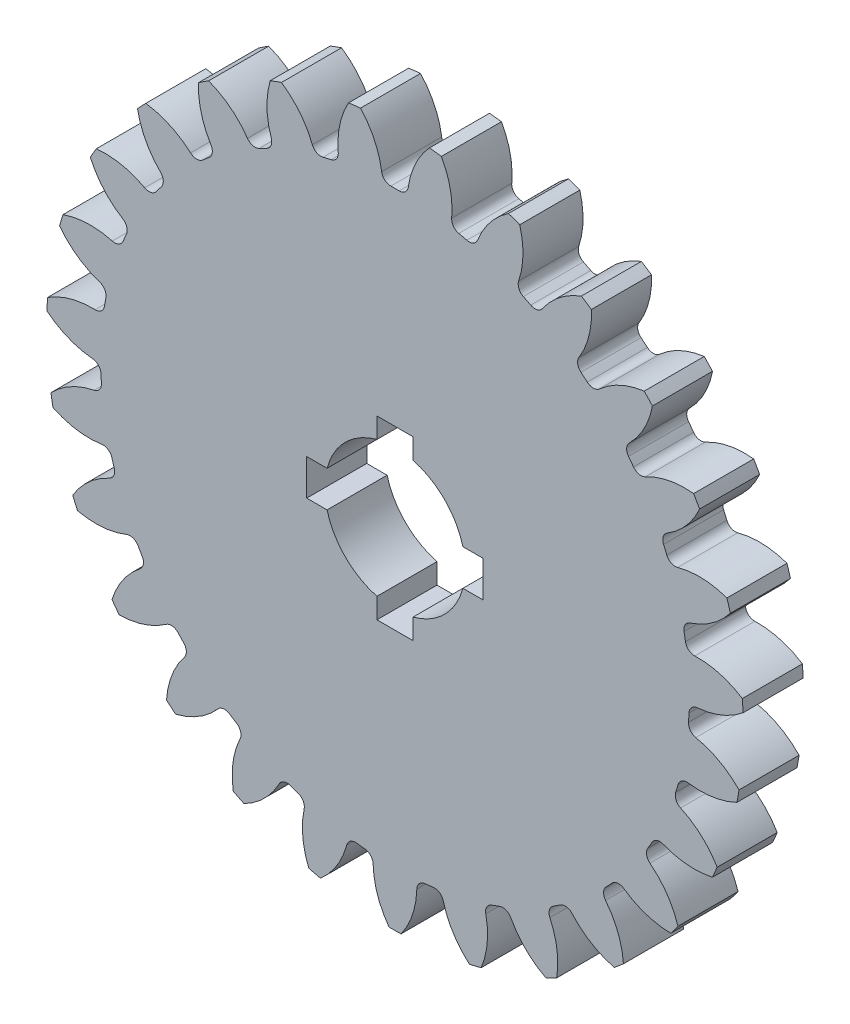
SolidWorks part; units mm, degrees
ref_plane "Front Plane" through (0, 0, 0) normal (0, 0, 1) x (1, 0, 0)
ref_plane "Top Plane" through (0, 0, 0) normal (0, 1, 0) x (1, 0, 0)
ref_plane "Right Plane" through (0, 0, 0) normal (1, 0, 0) x (0, 0, -1)
sketch "Sketch1" plane through (0, 0, 0) normal (0, 0, 1) x (1, 0, 0)
  line L4 (-1.0463, 24.4776) -> (0, 0) construction
  line L5 (0, 0) -> (0, 29) construction
  line L6 (0, 0) -> (3.3667, 28.8039) construction
  line L7 (-1.6208, 26.9513) -> (0.7728, 27.9892) construction
  line L8 (-1.6208, 26.9513) -> (0.4007, 27.0729) construction
  line L11 (1.6208, 26.9513) -> (-1.6208, 26.9513) construction
  circle A0 centre (0, 0) radius 24.5
  circle A1 centre (0, 0) radius 27 construction
  circle A2 centre (0, 0) radius 29
  arc A3 (-2.8696, 28.8577) -> (-1.0463, 24.4776) centre (-7.9254, 24.1836) cw
  arc A4 (2.8696, 28.8577) -> (1.0463, 24.4776) centre (7.9254, 24.1836) ccw
  point P5 (-27, 0)
  point P6 (-29, 0)
  point P7 (-24.5, 0)
  point P12 (-1.6208, 26.9513)
  point P22 (1.6208, 26.9513)
  dimension "D5" = 54
  dimension "D1" = 2.5
  dimension "D2" = 2
  dimension "D3" = 20
  dimension "D4" = 3.2416
  dimension "D6" = 6.667
  dimension "D7" = 0.5
extrude "Boss-Extrude1" add sketch "Sketch1" against normal blind 5 contours A2
extrude "Cut-Extrude1" cut sketch "Sketch1<4>" against normal blind 10 contours A4 A2 A3 A0 region at (0, 27.1314, 0)
sketch "Sketch1<4>" plane through (0, 0, 0) normal (0, 0, 1) x (1, 0, 0) same geometry as "Sketch1"
fillet "Fillet2" radius 0.76 2 edges at (1.0463, 24.4776, -2.5) (-1.0463, 24.4776, -2.5)
ref_axis "Axis1" through (0, 0, 0) along (0, 0, 1)
pattern_circular "CirPattern2" count 27 over 360 about axis through (0, 0, 0) along (0, 0, 1) of "Cut-Extrude1", "Fillet2"
sketch "Sketch2" plane through (0, 0, 0) normal (0, 0, 1) x (1, 0, 0)
  line L0 (-1.5, 5.6528) -> (-1.5, 7.3485)
  line L1 (-1.5, 4.3485) -> (1.5, 4.3485) construction
  line L2 (-1.5, 4.3485) -> (-1.5, 7.3485) construction
  line L3 (-1.5, 7.3485) -> (1.5, 7.3485) construction
  line L4 (1.5, 4.3485) -> (1.5, 7.3485) construction
  line L5 (-1.5, 4.3485) -> (1.5, 7.3485) construction
  line L6 (-1.5, 7.3485) -> (1.5, 4.3485) construction
  line L7 (4.3485, -1.5) -> (7.3485, -1.5) construction
  line L8 (4.3485, -1.5) -> (4.3485, 1.5) construction
  line L9 (4.3485, 1.5) -> (7.3485, 1.5) construction
  line L10 (7.3485, -1.5) -> (7.3485, 1.5) construction
  line L11 (4.3485, -1.5) -> (7.3485, 1.5) construction
  line L12 (4.3485, 1.5) -> (7.3485, -1.5) construction
  line L13 (-1.5, -7.3485) -> (1.5, -7.3485) construction
  line L14 (-1.5, -7.3485) -> (-1.5, -4.3485) construction
  line L15 (-1.5, -4.3485) -> (1.5, -4.3485) construction
  line L16 (1.5, -7.3485) -> (1.5, -4.3485) construction
  line L17 (-1.5, -7.3485) -> (1.5, -4.3485) construction
  line L18 (-1.5, -4.3485) -> (1.5, -7.3485) construction
  line L19 (-7.3485, -1.5) -> (-4.3485, -1.5) construction
  line L20 (-7.3485, -1.5) -> (-7.3485, 1.5) construction
  line L21 (-7.3485, 1.5) -> (-4.3485, 1.5) construction
  line L22 (-4.3485, -1.5) -> (-4.3485, 1.5) construction
  line L23 (-7.3485, -1.5) -> (-4.3485, 1.5) construction
  line L24 (-7.3485, 1.5) -> (-4.3485, -1.5) construction
  line L25 (-1.5, 7.3485) -> (1.5, 7.3485)
  line L26 (1.5, 7.3485) -> (1.5, 5.6528)
  line L27 (5.6528, 1.5) -> (7.3485, 1.5)
  line L28 (7.3485, 1.5) -> (7.3485, -1.5)
  line L29 (7.3485, -1.5) -> (5.6528, -1.5)
  line L30 (1.5, -7.3485) -> (1.5, -5.6528)
  line L31 (1.5, -7.3485) -> (-1.5, -7.3485)
  line L32 (-1.5, -7.3485) -> (-1.5, -5.6528)
  line L33 (-5.6528, -1.5) -> (-7.3485, -1.5)
  line L34 (-7.3485, -1.5) -> (-7.3485, 1.5)
  line L35 (-7.3485, 1.5) -> (-5.6528, 1.5)
  circle A0 centre (0, 0) radius 7.5 construction
  arc A1 (-1.5, 5.6528) -> (-5.6528, 1.5) centre (0, 0) ccw
  arc A2 (5.6528, 1.5) -> (1.5, 5.6528) centre (0, 0) ccw
  arc A3 (1.5, -5.6528) -> (5.6528, -1.5) centre (0, 0) ccw
  arc A4 (-5.6528, -1.5) -> (-1.5, -5.6528) centre (0, 0) ccw
  point P3 (0, 5.8485)
  point P8 (5.8485, 0)
  point P13 (0, -5.8485)
  point P18 (-5.8485, 0)
  dimension "D1" = 15
  dimension "D2" = 3
extrude "Cut-Extrude2" cut sketch "Sketch2" against normal up to surface (5 mm away) up to face at (0, 0, -5)
equation "\"backlash\"= 0.1mm"
equation "\"module\"= 2mm"
equation "\"pressureAngle\"= 20deg"
equation "\"width\"= 10mm"
equation "\"D1@Sketch1\"= 1.25 * \"module\""
equation "\"D2@Sketch1\"=\"module\""
equation "\"D5@Sketch1\"=\"module\"*\"numberOfTeeth\""
equation "\"D1@Boss-Extrude1\"=\"width\"-5"
equation "\"D3@Sketch1\"=\"pressureAngle\""
equation "\"D1@Cut-Extrude1\"=\"width\""
equation "\"D1@CirPattern2\"=\"numberOfTeeth\""
equation "\"D1@Fillet2\"=0.38*\"module\""
equation "\"D4@Sketch1\"=pi*\"module\"/2+\"backlash\""
equation "\"numberOfTeeth\"= 27"
equation "\"D6@Sketch1\"=180/\"numberOfTeeth\""
equation "\"toothTipProfile\"= 1mm"
equation "\"D7@Sketch1\"=\"toothTipProfile\"/2"
equation "\"lengthOverallRack\"= pi * \"module\" * \"numberOfTeethRack\""
equation "\"numberOfTeethRack\"= 20"
